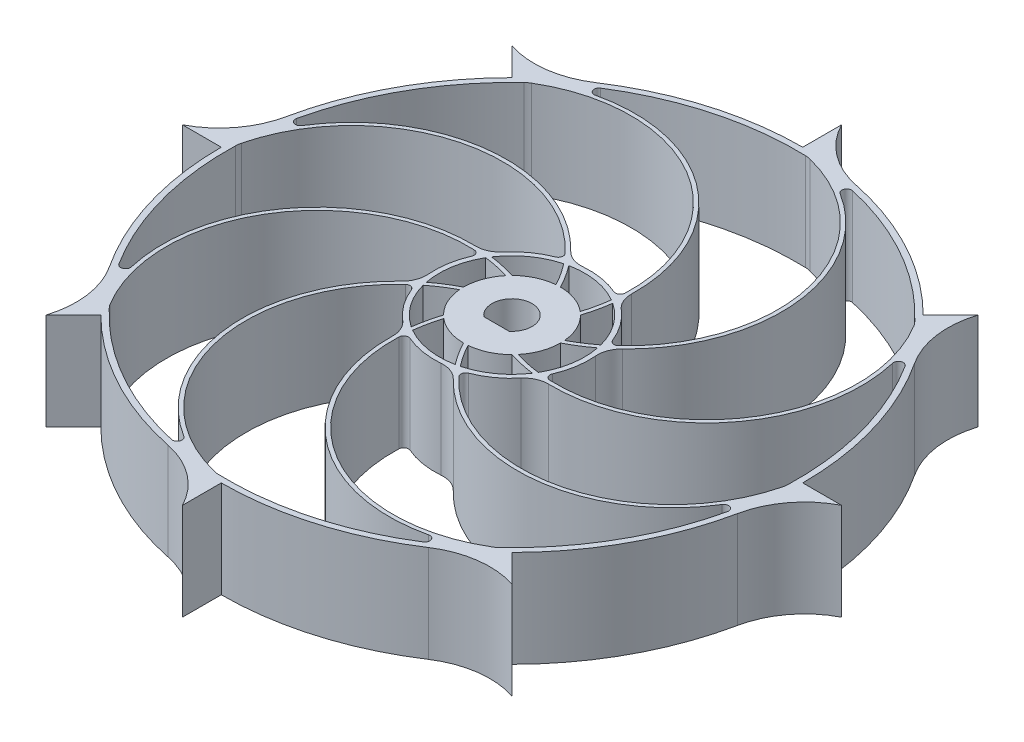
SolidWorks part; units mm, degrees
material "PET"
ref_plane "Front Plane" through (0, 0, 0) normal (0, 0, 1) x (1, 0, 0)
ref_plane "Top Plane" through (0, 0, 0) normal (0, 1, 0) x (1, 0, 0)
ref_plane "Right Plane" through (0, 0, 0) normal (1, 0, 0) x (0, 0, -1)
sketch "Sketch1" plane through (0, 0, 0) normal (0, 1, 0) x (1, 0, 0)
  line L0 (-2.603, -3.2) -> (2.603, -3.2)
  arc A0 (2.603, -3.2) -> (-2.603, -3.2) centre (0, 0) ccw
  circle A1 centre (0, 0) radius 60
  circle A28 centre (0, 0) radius 10
  circle A29 centre (0, 0) radius 58.8
  point P78 (0, 0)
  dimension "D1" = 8.25
  dimension "D2" = 120
  dimension "D3" = 20
  dimension "D7" = 3.2
  dimension "D4" = 1.2
extrude "Boss-Extrude1" add sketch "Sketch1" along normal blind 20 contours A1 A29 | A28 A0 L0 region at (-59.8303, 0, 0) region at (-9.7172, 0, 0)
sketch "Sketch4" plane through (0, 0, 0) normal (0, 1, 0) x (1, 0, 0)
  line L0 (-9.6325, -0.7106) -> (-10, 0)
  line L1 (0.1172, -59.2086) -> (0, -60)
  arc A0 (0, -60) -> (-10, 0) centre (4.6819, -28.3864) cw
  circle A1 centre (0, 0) radius 60 construction
  circle A2 centre (0, 0) radius 10 construction
  arc A3 (0.1172, -59.2086) -> (-9.6325, -0.7106) centre (4.6819, -28.3864) cw
  dimension "D1" = 0.8
extrude "Boss-Extrude4" add sketch "Sketch4" along normal up to surface (20 mm away) up to face at (0, 20, 58.8)
ref_axis "Axis1" through (0, 21, 0) along (0, -1, 0)
pattern_circular "CirPattern1" count 8 over 360 about axis through (0, 21, 0) along (0, -1, 0) of "Boss-Extrude4"
sketch "Sketch2" plane through (0, 0, 0) normal (0, 1, 0) x (1, 0, 0)
  circle A0 centre (0, 0) radius 15
  circle A1 centre (0, 0) radius 16
  dimension "D1" = 30
  dimension "D2" = 1
extrude "Boss-Extrude2" add sketch "Sketch2" along normal up to surface (20 mm away) up to face at (21.0377, 20, 26.1005)
sketch "Sketch3" plane through (0, 0, 0) normal (0, 1, 0) x (1, 0, 0)
  line L0 (0, -60) -> (0, -68)
  line L6 (-42.4264, -42.4264) -> (-48.0833, -48.0833)
  line L7 (-60, 0) -> (-68, 0)
  line L8 (-42.4264, 42.4264) -> (-48.0833, 48.0833)
  line L9 (0, 60) -> (0, 68)
  line L10 (42.4264, 42.4264) -> (48.0833, 48.0833)
  line L11 (60, 0) -> (68, 0)
  line L12 (42.4264, -42.4264) -> (48.0833, -48.0833)
  arc A0 (-48.0833, -48.0833) -> (-50.1745, -32.9017) centre (-65.1067, -42.6934) ccw
  arc A1 (0, -68) -> (-12.2137, -58.7437) centre (-15.8486, -76.2261) ccw
  arc A13 (-68, 0) -> (-58.7437, 12.2137) centre (-76.2261, 15.8486) ccw
  arc A15 (-48.0833, 48.0833) -> (-32.9017, 50.1745) centre (-42.6934, 65.1067) ccw
  circle A17 centre (0, 0) radius 60 construction
  circle A18 centre (0, 0) radius 60
  arc A19 (0, 68) -> (12.2137, 58.7437) centre (15.8486, 76.2261) ccw
  arc A20 (48.0833, 48.0833) -> (50.1745, 32.9017) centre (65.1067, 42.6934) ccw
  arc A21 (68, 0) -> (58.7437, -12.2137) centre (76.2261, -15.8486) ccw
  arc A22 (48.0833, -48.0833) -> (32.9017, -50.1745) centre (42.6934, -65.1067) ccw
  arc A23 (-58.7437, 12.2137) -> (-60, 0) centre (0, 0) ccw
  arc A24 (60, 0) -> (58.7437, -12.2137) centre (0, 0) cw
  point P30 (0, 0)
  point P33 (-2.1651, 1.25)
  point P42 (0, 0)
  dimension "D1" = 8
  dimension "D2" = 8
extrude "Boss-Extrude3" add sketch "Sketch3" along normal up to surface (20 mm away) contours A18 | A18 A1 L0 | A18 | A18 | A18 | A18 | A18 A13 L7 | A21 L11 A18 region at (-2.8725, 0, 62.1395) region at (41.9081, 0, 45.9704) region at (-45.9704, 0, 41.9081) region at (62.1395, 0, 2.8725) region at (-62.1395, 0, -2.8725) region at (45.9704, 0, -41.9081) region at (-41.9081, 0, -45.9704) region at (2.8725, 0, -62.1395) up to face at (-10.3369, 20, 6.247)
fillet "Fillet1" radius 1 16 edges at (7.6573, 10, -14.0487) (15.3485, 10, -4.5193) (14.0487, 10, 7.6573) (4.5193, 10, 15.3485) (-7.6573, 10, 14.0487) (-15.3485, 10, 4.5193) (-14.0487, 10, -7.6573) (-4.5193, 10, -15.3485) (-6.0542, 10, 58.4875) (37.0759, 10, 45.6379) (58.4875, 10, 6.0542) (45.6379, 10, -37.0759) (6.0542, 10, -58.4875) (-37.0759, 10, -45.6379) (-58.4875, 10, -6.0542) (-45.6379, 10, 37.0759)
fillet "Fillet2" radius 5 16 edges at (-8.4195, 10, 13.6056) (-15.5741, 10, 3.6672) (-13.6056, 10, -8.4195) (-3.6672, 10, -15.5741) (8.4195, 10, -13.6056) (15.5741, 10, -3.6672) (13.6056, 10, 8.4195) (3.6672, 10, 15.5741) (-58.7555, 10, -2.2868) (-39.9294, 10, -43.1635) (2.2868, 10, -58.7555) (43.1635, 10, -39.9294) (58.7555, 10, 2.2868) (39.9294, 10, 43.1635) (-2.2868, 10, 58.7555) (-43.1635, 10, 39.9294)
